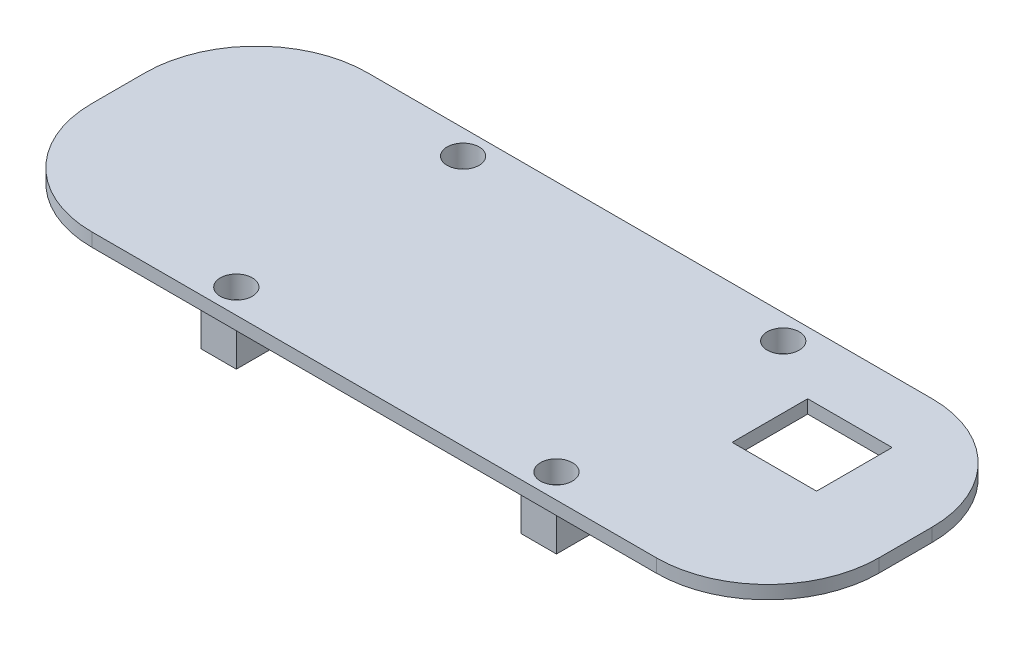
SolidWorks part; units mm, degrees
ref_plane "Front Plane" through (0, 0, 0) normal (0, 0, 1) x (1, 0, 0)
ref_plane "Top Plane" through (0, 0, 0) normal (0, 1, 0) x (1, 0, 0)
ref_plane "Right Plane" through (0, 0, 0) normal (1, 0, 0) x (0, 0, -1)
sketch "Sketch1" plane through (0, 0, 0) normal (0, 1, 0) x (1, 0, 0)
  line L1 (0, 0) -> (177, 0)
  line L2 (0, 0) -> (0, 62)
  line L3 (0, 62) -> (177, 62)
  line L4 (177, 0) -> (177, 62)
  dimension "D1" = 177
  dimension "D2" = 62
extrude "Boss-Extrude1" add sketch "Sketch1" along normal blind 70
fillet "Fillet1" radius 25 4 edges at (177, 35, -62) (177, 35, 0) (0, 35, -62) (0, 35, 0)
sketch "Sketch3" plane through (0, 70, 0) normal (0, 1, 0) x (1, 0, 0)
  line L0 (177, 25) -> (177, 37) construction
  line L1 (152, 62) -> (25, 62) construction
  line L2 (138, 31) -> (157, 31)
  line L3 (138, 31) -> (138, 48)
  line L4 (138, 48) -> (157, 48)
  line L5 (157, 31) -> (157, 48)
  dimension "D1" = 17
  dimension "D2" = 19
  dimension "D3" = 20
  dimension "D4" = 14
extrude "Cut-Extrude1" cut sketch "Sketch3" against normal blind 70
ref_plane "Plane1" through (0, 67, 0) normal (0, 1, 0) x (1, 0, 0)
sketch "Sketch9" plane through (0, 67, 0) normal (0, 1, 0) x (1, 0, 0)
  line L0 (25, 59) -> (152, 59)
  line L1 (25, 3) -> (152, 3)
  line L2 (174, 25) -> (174, 37)
  line L3 (3, 37) -> (3, 25)
  line L6 (177, 25) -> (177, 37) construction
  arc A0 (25, 59) -> (3, 37) centre (25, 37) ccw
  arc A1 (25, 3) -> (3, 25) centre (25, 25) cw
  arc A2 (152, 59) -> (174, 37) centre (152, 37) cw
  arc A3 (152, 3) -> (174, 25) centre (152, 25) ccw
  point P26 (177, 31)
  dimension "D1" = 3
extrude "Cut-Extrude5" cut sketch "Sketch9" against normal blind 64
sketch "Sketch11" plane through (0, 0, 0) normal (0, -1, 0) x (1, 0, 0)
  line L0 (0, -37) -> (0, -25) construction
  line L1 (25, 0) -> (152, 0) construction
  circle A0 centre (31, -31) radius 25
  dimension "D1" = 50
  dimension "D2" = 31
  dimension "D3" = 31
sketch "Sketch15" plane through (0, 0, 0) normal (0, -1, 0) x (1, 0, 0)
  line L0 (125, -7) -> (121, -3)
  line L1 (121, -3) -> (119, -3)
  line L2 (25, -3) -> (152, -3) construction
  line L3 (119, -3) -> (119, -7.5)
  line L4 (119, -7.5) -> (125, -7.5)
  line L5 (125, -29.5) -> (125, -7) construction
  line L6 (125, -7.5) -> (125, -7)
  line L7 (137, -7) -> (137, -7.5)
  line L8 (137, -7) -> (137, -29.5) construction
  line L9 (137, -7.5) -> (143, -7.5)
  line L10 (143, -7.5) -> (143, -3)
  line L11 (143, -3) -> (141, -3)
  line L12 (141, -3) -> (137, -7)
  dimension "D1" = 4.5
  dimension "D2" = 6
extrude "Boss-Extrude7" add sketch "Sketch15" against normal blind 33
sketch "Sketch16" plane through (0, 0, 0) normal (0, -1, 0) x (1, 0, 0)
  line L0 (25, -3) -> (119, -3) construction
  line L1 (56, -3) -> (61, -3)
  line L2 (56, -3) -> (56, -8)
  line L3 (56, -8) -> (61, -8)
  line L4 (61, -3) -> (61, -8)
  line L6 (61, -40.5) -> (61, -44)
  line L7 (102, -8) -> (107, -8)
  line L8 (102, -8) -> (102, -3)
  line L9 (102, -3) -> (107, -3)
  line L10 (107, -8) -> (107, -3)
  line L11 (61, -44) -> (101, -44)
  line L12 (101, -44) -> (101, -40.5)
  line L13 (101, -40.5) -> (106, -40.5)
  line L14 (106, -40.5) -> (106, -59)
  line L15 (152, -59) -> (25, -59) construction
  line L16 (106, -59) -> (56, -59)
  line L17 (56, -59) -> (56, -40.5)
  line L18 (56, -40.5) -> (61, -40.5)
  line L19 (61, -40.5) -> (61, -6.5) construction
  dimension "D1" = 41
  dimension "D2" = 5
extrude "Boss-Extrude8" add sketch "Sketch16" against normal blind 40
extrude "Cut-Extrude9" cut sketch "Sketch11" against normal blind 5.5
sketch "Sketch22" plane through (0, 70, 0) normal (0, 1, 0) x (1, 0, 0)
  line L0 (0, 37) -> (0, 25) construction
  circle A0 centre (31, 31) radius 28.5
  point P4 (0, 31)
  dimension "D1" = 57
  dimension "D2" = 31
extrude "Boss-Extrude20" add sketch "Sketch22" against normal blind 21
sketch "Sketch21" plane through (0, 70, 0) normal (0, 1, 0) x (1, 0, 0)
  line L0 (0, 37) -> (0, 25) construction
  circle A0 centre (31, 31) radius 25
  point P5 (0, 31)
  dimension "D1" = 50
  dimension "D2" = 31
sketch "Sketch24" plane through (0, 0, 0) normal (0, -1, 0) x (1, 0, 0)
  line L0 (123.5, -7.5) -> (125, -7.5)
  line L1 (125, -29.5) -> (125, -7) construction
  line L2 (125, -7.5) -> (125, -29.5)
  line L3 (125, -29.5) -> (137, -29.5)
  line L4 (137, -29.5) -> (137, -7.5)
  line L5 (137, -7) -> (137, -29.5) construction
  line L6 (137, -7.5) -> (138.5, -7.5)
  line L7 (138.5, -7.5) -> (138.5, -35.5)
  line L8 (138.5, -35.5) -> (123.5, -35.5)
  line L9 (123.5, -35.5) -> (123.5, -7.5)
  line L10 (143, -7.5) -> (137, -7.5) construction
  line L14 (138.5, -55.5) -> (138.5, -35.5) construction
  line L15 (128.5, -35.5) -> (138.5, -35.5) construction
  dimension "D1" = 15
extrude "Boss-Extrude21" add sketch "Sketch24" against normal blind 10
sketch "Sketch25" plane through (0, 0, 0) normal (0, -1, 0) x (1, 0, 0)
  line L0 (134.5, -35.5) -> (134.5, -31.5)
  line L1 (134.5, -31.5) -> (124.5, -31.5)
  line L2 (124.5, -31.5) -> (124.5, -45.5)
  line L3 (124.5, -45.5) -> (128.5, -45.5)
  line L4 (128.5, -45.5) -> (128.5, -35.5)
  line L5 (128.5, -35.5) -> (134.5, -35.5)
  line L6 (160.5, -35.5) -> (166.5, -35.5)
  line L7 (166.5, -35.5) -> (166.5, -45.5)
  line L8 (166.5, -45.5) -> (170.5, -45.5)
  line L9 (170.5, -45.5) -> (170.5, -31.5)
  line L10 (170.5, -31.5) -> (160.5, -31.5)
  line L11 (160.5, -31.5) -> (160.5, -35.5)
  line L12 (166.5, -35.5) -> (166.5, -45.5) construction
  line L13 (128.5, -45.5) -> (128.5, -35.5) construction
  line L14 (128.5, -35.5) -> (138.5, -35.5) construction
  line L15 (166.5, -35.5) -> (156.5, -35.5) construction
  dimension "D1" = 10
  dimension "D2" = 14
  dimension "D3" = 4
extrude "Boss-Extrude22" add sketch "Sketch25" against normal blind 40
sketch "Sketch26" plane through (0, 0, 0) normal (0, -1, 0) x (1, 0, 0)
  line L0 (25, 0) -> (152, 0)
  line L1 (177, -25) -> (177, -37)
  line L2 (152, -62) -> (25, -62)
  line L3 (0, -25) -> (0, -37)
  line L4 (0, -37) -> (0, -25) construction
  line L6 (138, -48) -> (157, -48)
  line L7 (138, -48) -> (138, -31)
  line L8 (138, -31) -> (157, -31)
  line L9 (157, -48) -> (157, -31)
  arc A0 (0, -37) -> (25, -62) centre (25, -37) ccw construction
  arc A1 (25, 0) -> (0, -25) centre (25, -25) ccw
  arc A2 (0, -37) -> (25, -62) centre (25, -37) ccw
  arc A3 (152, -62) -> (177, -37) centre (152, -37) ccw
  arc A4 (177, -25) -> (152, 0) centre (152, -25) ccw
  circle A5 centre (31, -31) radius 25
  circle A6 centre (31, -31) radius 25 construction
extrude "Boss-Extrude23" add sketch "Sketch26" along normal blind 1
sketch "Sketch27" plane through (0, 0, 0) normal (-1, 0, 0) x (0, 0, 1)
  line L0 (-37, 70) -> (-25, 70) construction
  line L1 (-51, 29.5) -> (-11, 29.5)
  line L2 (-51, 29.5) -> (-51, 39.5)
  line L3 (-51, 39.5) -> (-11, 39.5)
  line L4 (-11, 29.5) -> (-11, 39.5)
  line L5 (-51, 29.5) -> (-11, 39.5) construction
  line L6 (-51, 39.5) -> (-11, 29.5) construction
  line L7 (-25, -1) -> (-25, 70) construction
  point P0 (-31, 34.5)
  point P8 (-31, 70)
  point P12 (-25, 34.5)
  dimension "D1" = 40
  dimension "D2" = 10
extrude "Cut-Extrude12" cut sketch "Sketch27" against normal blind 10
sketch "Sketch28" plane through (0, -1, 0) normal (0, -1, 0) x (1, 0, 0)
  line L0 (152, -59) -> (106, -59) construction
  line L1 (106, -40.5) -> (106, -59) construction
  line L2 (110, -59) -> (120, -59)
  line L3 (110, -59) -> (110, -49)
  line L4 (110, -49) -> (120, -49)
  line L5 (120, -59) -> (120, -49)
  dimension "D1" = 10
  dimension "D2" = 10
  dimension "D3" = 4
extrude "Cut-Extrude13" cut sketch "Sketch28" against normal blind 5
ref_plane "Plane2" through (0, 67, 0) normal (0, 1, 0) x (1, 0, 0)
sketch "Sketch30" plane through (0, 67, 0) normal (0, 1, 0) x (1, 0, 0)
  line L0 (0, 37) -> (0, 25) construction
  line L1 (25, 58) -> (152, 58)
  line L2 (4, 37) -> (4, 25)
  line L3 (25, 4) -> (152, 4)
  line L4 (173, 37) -> (173, 25)
  line L5 (177, 25) -> (177, 37) construction
  line L6 (25, 0) -> (152, 0) construction
  line L7 (152, 62) -> (25, 62) construction
  line L9 (-8.7918, 65.1377) -> (185.5455, 65.1377)
  line L10 (-8.7918, 65.1377) -> (-8.7918, -2.9849)
  line L11 (-8.7918, -2.9849) -> (185.5455, -2.9849)
  line L12 (185.5455, 65.1377) -> (185.5455, -2.9849)
  arc A0 (152, 58) -> (173, 37) centre (152, 37) cw
  arc A1 (152, 4) -> (173, 25) centre (152, 25) ccw
  arc A2 (4, 25) -> (25, 4) centre (25, 25) ccw
  arc A3 (25, 58) -> (4, 37) centre (25, 37) ccw
  point P8 (177, 31)
  dimension "D5" = 21
  dimension "D1" = 4
  dimension "D2" = 4
  dimension "D3" = 4
  dimension "D4" = 4
extrude "Cut-Extrude14" cut sketch "Sketch30" against normal blind 0.1
sketch "Sketch31" plane through (0, 67, 0) normal (0, 1, 0) x (1, 0, 0)
  line L0 (152, 3) -> (36.3151, 3) construction
  line L1 (0, 37) -> (0, 25) construction
  line L2 (177, 25) -> (177, 37) construction
  line L3 (36.3151, 59) -> (152, 59) construction
  line L4 (25, 0) -> (152, 0) construction
  circle A0 centre (52, 56.5) radius 3.5
  circle A1 centre (52, 5.5) radius 3.5
  circle A2 centre (164.5563, 10) radius 3.5
  circle A3 centre (124, 56.5) radius 3.5
  arc A4 (152, 3) -> (174, 25) centre (152, 25) ccw construction
  point P22 (167.5563, 9.4437)
  dimension "D1" = 7
  dimension "D2" = 2.5
  dimension "D3" = 52
  dimension "D4" = 53
  dimension "D5" = 2.5
  dimension "D6" = 3
  dimension "D7" = 10
extrude "Cut-Extrude17" cut sketch "Sketch26<3>" against normal blind 45 and the other way blind 58
sketch "Sketch26<3>" plane through (0, 0, 0) normal (0, -1, 0) x (1, 0, 0) same geometry as "Sketch26"
sketch "Sketch36" plane through (0, 45, 0) normal (0, -1, 0) x (1, 0, 0)
  line L0 (25, -3) -> (152, -3)
  line L1 (174, -25) -> (174, -37)
  line L2 (152, -59) -> (25.6849, -59)
  line L3 (3, -37) -> (3, -25)
  line L4 (25, 0) -> (152, 0)
  line L5 (177, -25) -> (177, -37)
  line L6 (177, -37) -> (177, -25) construction
  line L7 (152, -62) -> (25, -62)
  line L8 (0, -37) -> (0, -25)
  arc A0 (152, -3) -> (174, -25) centre (152, -25) cw
  arc A1 (174, -37) -> (152, -59) centre (152, -37) cw
  arc A2 (25.6849, -59) -> (3, -37) centre (25.6849, -36.3044) cw
  arc A3 (3, -25) -> (25, -3) centre (25, -25) cw
  arc A4 (152, 0) -> (177, -25) centre (152, -25) cw
  arc A5 (177, -25) -> (152, 0) centre (152, -25) ccw construction
  arc A6 (152, -62) -> (177, -37) centre (152, -37) ccw construction
  arc A7 (177, -37) -> (152, -62) centre (152, -37) cw
  arc A8 (25, -62) -> (0, -37) centre (25, -37) cw
  arc A9 (0, -25) -> (25, 0) centre (25, -25) cw
  arc M9 (25, 0) -> (0, -25) centre (25, -25) ccw
  line M10 (0, -25) -> (0, -37)
  arc M11 (0, -37) -> (25, -62) centre (25, -37) ccw
  line M12 (25, -62) -> (152, -62)
  arc M13 (152, -62) -> (177, -37) centre (152, -37) ccw
  line M14 (177, -37) -> (177, -25)
  arc M15 (177, -25) -> (152, 0) centre (152, -25) ccw
  line M16 (152, 0) -> (25, 0)
  arc M17 (25, -59) -> (3, -37) centre (25, -37) cw
  line M18 (3, -37) -> (3, -25)
  arc M19 (3, -25) -> (25, -3) centre (25, -25) cw
  line M20 (25, -3) -> (152, -3)
  arc M21 (152, -3) -> (174, -25) centre (152, -25) cw
  line M22 (174, -25) -> (174, -37)
  arc M23 (174, -37) -> (152, -59) centre (152, -37) cw
  line M24 (152, -59) -> (25, -59)
extrude "Cut-Extrude25" cut sketch "Sketch36" against normal up to surface (22 mm away) contours M16 M9 M10 M11 M12 M13 M14 M15 M24 M17 M18 M19 M20 M21 M22 M23 | A9 L4 A4 L5 A7 L7 A8 L8 | A3 L0 A0 L1 A1 L2 A2 L3 region at (88.5, 45, -1.8754) up to face at (20.4124, 67, -31)
sketch "Sketch38" plane through (0, 70, 0) normal (0, 1, 0) x (1, 0, 0)
  line L0 (124, 56.5) -> (124, -15.2432) construction
  line L1 (48, 60.5) -> (56, 60.5)
  line L2 (48, 60.5) -> (48, 52.5)
  line L3 (48, 52.5) -> (56, 52.5)
  line L4 (56, 60.5) -> (56, 52.5)
  line L5 (48, 60.5) -> (56, 52.5) construction
  line L6 (48, 52.5) -> (56, 60.5) construction
  line L7 (120, 60.5) -> (128, 60.5)
  line L8 (120, 60.5) -> (120, 52.5)
  line L9 (120, 52.5) -> (128, 52.5)
  line L10 (128, 60.5) -> (128, 52.5)
  line L11 (120, 60.5) -> (128, 52.5) construction
  line L12 (120, 52.5) -> (128, 60.5) construction
  line L13 (48, 9.5) -> (56, 9.5)
  line L14 (48, 9.5) -> (48, 1.5)
  line L15 (48, 1.5) -> (56, 1.5)
  line L16 (56, 9.5) -> (56, 1.5)
  line L17 (48, 9.5) -> (56, 1.5) construction
  line L18 (48, 1.5) -> (56, 9.5) construction
  line L24 (120, 9.5) -> (128, 9.5)
  line L25 (52, 5.5) -> (124, 5.5) construction
  line L26 (120, 9.5) -> (120, 1.5)
  line L27 (120, 1.5) -> (128, 1.5)
  line L28 (128, 9.5) -> (128, 1.5)
  line L29 (120, 9.5) -> (128, 1.5) construction
  line L30 (120, 1.5) -> (128, 9.5) construction
  point P0 (52, 56.5)
  point P6 (124, 56.5)
  point P12 (52, 5.5)
  point P18 (124.2515, 4.6593)
  dimension "D1" = 8
  dimension "D2" = 8
  dimension "D3" = 8
  dimension "D4" = 8
  dimension "D5" = 8
  dimension "D6" = 8
  dimension "D7" = 8
  dimension "D8" = 8
extrude "Boss-Extrude26" add sketch "Sketch38" against normal blind 12
sketch "Sketch41" plane through (0, 70, 0) normal (0, 1, 0) x (1, 0, 0)
  line L0 (124, 56.5) -> (124, 5.5) construction
  line L1 (52, 5.5) -> (131.9582, 5.5) construction
  circle A0 centre (52, 56.5) radius 3.6
  circle A1 centre (124, 56.5) radius 3.6
  circle A2 centre (52, 5.5) radius 3.6
  circle A3 centre (124, 5.5) radius 3.6
  dimension "D1" = 7.2
extrude "Cut-Extrude28" cut sketch "Sketch41" against normal blind 5
sketch "Sketch44" plane through (0, 58, 0) normal (0, -1, 0) x (1, 0, 0)
  line L0 (52, -5.5) -> (139.6786, -5.5) construction
  line L1 (124, -56.5) -> (124, -5.5) construction
  circle A0 centre (52, -5.5) radius 2.1
  circle A1 centre (124, -56.5) radius 2.1
  circle A2 centre (52, -56.5) radius 2.1
  circle A3 centre (124, -5.5) radius 2.1
extrude "Cut-Extrude29" cut sketch "Sketch44" against normal blind 8
extrude "Cut-Extrude30" cut sketch "Sketch22<2>" against normal blind 40 from surface starting at face at (124, 67, -5.5)
sketch "Sketch22<2>" plane through (0, 70, 0) normal (0, 1, 0) x (1, 0, 0) same geometry as "Sketch22"
sketch "Sketch45" plane through (0, 67, 0) normal (0, -1, 0) x (1, 0, 0)
  line L1 (132.4382, -22.5785) -> (152.3935, -22.5785)
  line L2 (132.4382, -22.5785) -> (132.4382, -46.7445)
  line L3 (132.4382, -46.7445) -> (152.3935, -46.7445)
  line L4 (152.3935, -22.5785) -> (152.3935, -46.7445)
extrude "Cut-Extrude31" cut sketch "Sketch45" along normal blind 112
